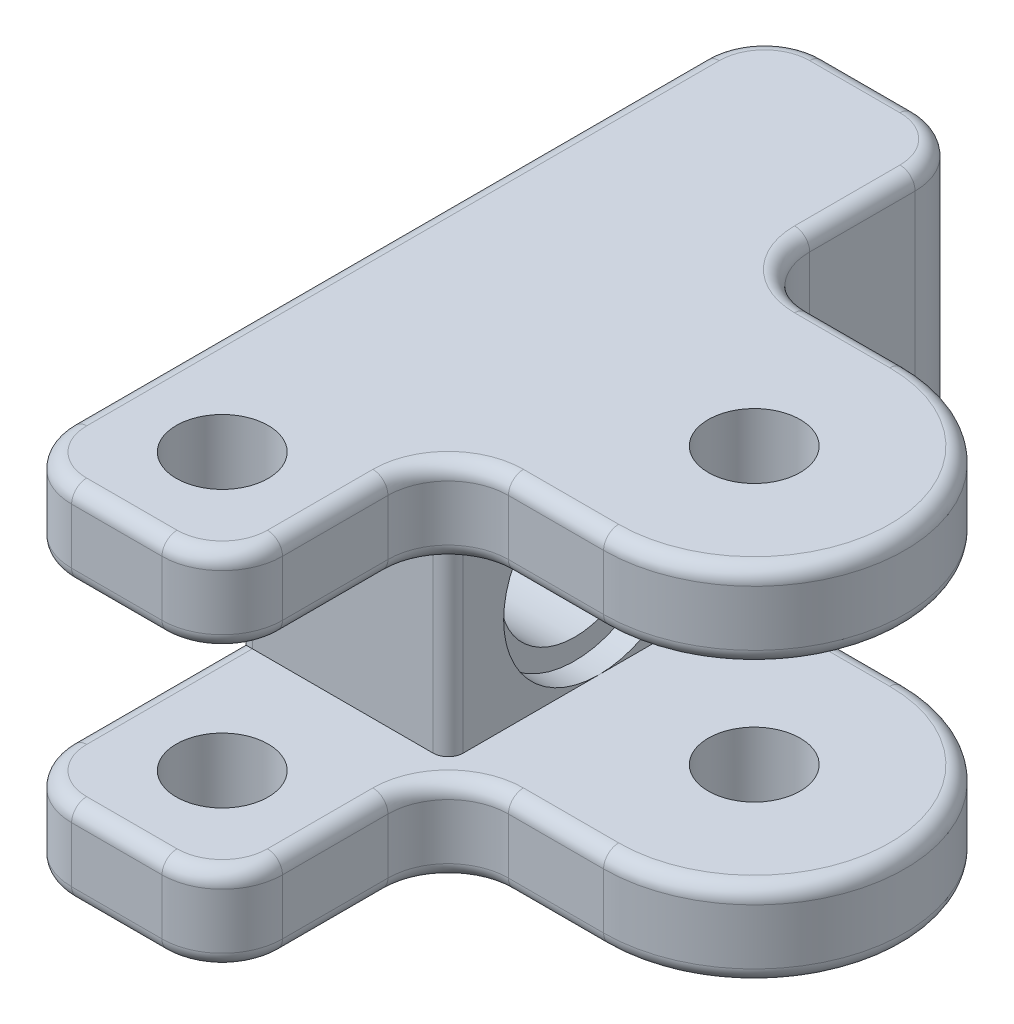
SolidWorks part; units mm, degrees
ref_plane "Front Plane" through (0, 0, 0) normal (0, 0, 1) x (1, 0, 0)
ref_plane "Top Plane" through (0, 0, 0) normal (0, 1, 0) x (1, 0, 0)
ref_plane "Right Plane" through (0, 0, 0) normal (1, 0, 0) x (0, 0, -1)
sketch "Sketch2" plane through (0, 0, 0) normal (0, 1, 0) x (1, 0, 0)
  line L0 (-5.16, -5) -> (-5.16, -12.5)
  line L1 (0, 5) -> (-5.16, 5)
  line L3 (0, -5) -> (-5.16, -5)
  line L5 (-5.16, 12.5) -> (-12.16, 12.5)
  line L6 (-5.16, 12.5) -> (-5.16, 5)
  line L7 (-5.16, -12.5) -> (-12.16, -12.5)
  line L8 (-12.16, 12.5) -> (-12.16, -12.5)
  circle A0 centre (0, 0) radius 1.525
  arc A1 (0, 5) -> (0, -5) centre (0, 0) cw
  circle A2 centre (-8.66, -9) radius 1.525
  point P10 (-12.16, 0)
  dimension "D5" = 3.05
  dimension "D6" = 3.05
  dimension "D1" = 5.16
  dimension "D2" = 10
  dimension "D3" = 7
  dimension "D4" = 25
  dimension "D7" = 3.5
extrude "Boss-Extrude1" add sketch "Sketch2" along normal blind 12
sketch "Sketch3" plane through (0, 0, 5) normal (0, 0, 1) x (1, 0, 0)
  line L1 (6.7543, 2.8413) -> (-5.16, 2.8413)
  line L2 (6.7543, 2.8413) -> (6.7543, 9.1587)
  line L3 (6.7543, 9.1587) -> (-5.16, 9.1587)
  line L4 (-5.16, 2.8413) -> (-5.16, 9.1587)
  line L5 (-5.16, 12) -> (-5.16, 0) construction
  dimension "D1" = 6.3175
extrude "Cut-Extrude1" cut sketch "Sketch3" against normal blind 12
fillet "Fillet2" radius 2 4 edges at (-5.16, 10.5794, -5) (-5.16, 1.4206, -5) (-5.16, 10.5794, 5) (-5.16, 1.4206, 5)
sketch "Sketch5" plane through (-12.16, 0, 0) normal (-1, 0, 0) x (0, 0, 1)
  circle A0 centre (0, 6) radius 2.475
  dimension "D1" = 4.95
extrude "Cut-Extrude3" cut sketch "Sketch5" against normal blind 13
sketch "Sketch6" plane through (0, 0, 12.5) normal (0, 0, 1) x (1, 0, 0)
  line L0 (-12.16, 12) -> (-12.16, 0) construction
  line L1 (-12.16, 9.1587) -> (-5.16, 9.1587)
  line L2 (-12.16, 9.1587) -> (-12.16, 2.8413)
  line L3 (-12.16, 2.8413) -> (-5.16, 2.8413)
  line L4 (-5.16, 9.1587) -> (-5.16, 2.8413)
  line L5 (0, 9.1587) -> (-3.16, 9.1587) construction
extrude "Cut-Extrude4" cut sketch "Sketch6" against normal up to vertex (7.5 mm away)
fillet "Fillet3" radius 2 6 edges at (-12.16, 6, -12.5) (-5.16, 6, -12.5) (-12.16, 10.5794, 12.5) (-5.16, 10.5794, 12.5) (-5.16, 1.4206, 12.5) (-12.16, 1.4206, 12.5)
sketch "Sketch8" plane through (-5.16, 0, 0) normal (1, 0, 0) x (0, 0, -1)
  line L1 (7, 2.8413) -> (-5, 2.8413) construction
  circle A0 centre (0, 6) radius 3.1588
  circle A2 centre (0, 6) radius 2.475
  circle A3 centre (0, 6) radius 2.475 construction
extrude "Cut-Extrude5" cut sketch "Sketch8" against normal blind 0.8
fillet "Fillet8" radius 0.5 46 edges at (-1.58, 0, -5) (5, 0, 0) (-12.16, 6, 5) (-12.16, 2.8413, 7.75) (-12.16, 9.1587, 7.75) (-5.16, 6, 5) (-12.16, 12, 0) (-12.16, 0, 0) (-5.16, 0, 8.75) (-8.66, 0, 12.5) (-8.66, 0, -12.5) (-11.5742, 0, 11.9142) (-5.7458, 0, 11.9142) (-5.7458, 0, -11.9142) (-11.5742, 0, -11.9142) (-8.66, 12, -12.5) (-8.66, 12, 12.5) (-5.16, 12, 8.75) (-5.7458, 12, 11.9142) (-11.5742, 12, 11.9142) (-5.7458, 12, -11.9142) (-11.5742, 12, -11.9142) (-8.66, 9.1587, 12.5) (-5.7458, 9.1587, 11.9142) (-11.5742, 9.1587, 11.9142) (-8.66, 2.8413, 12.5) (-11.5742, 2.8413, 11.9142) (-5.7458, 2.8413, 11.9142) (5, 2.8413, 0) (5, 9.1587, 0) (-1.58, 9.1587, -5) (5, 12, 0) (-5.16, 0, -8.75) (-5.16, 12, -8.75) (-1.58, 2.8413, -5) (-1.58, 12, 5) (-1.58, 0, 5) (-4.5742, 9.1587, -5.5858) (-4.5742, 12, -5.5858) (-4.5742, 0, -5.5858) (-4.5742, 2.8413, -5.5858) (-4.5742, 9.1587, 5.5858) (-4.5742, 12, 5.5858) (-4.5742, 0, 5.5858) (-4.5742, 2.8413, 5.5858) (-1.58, 12, -5)
